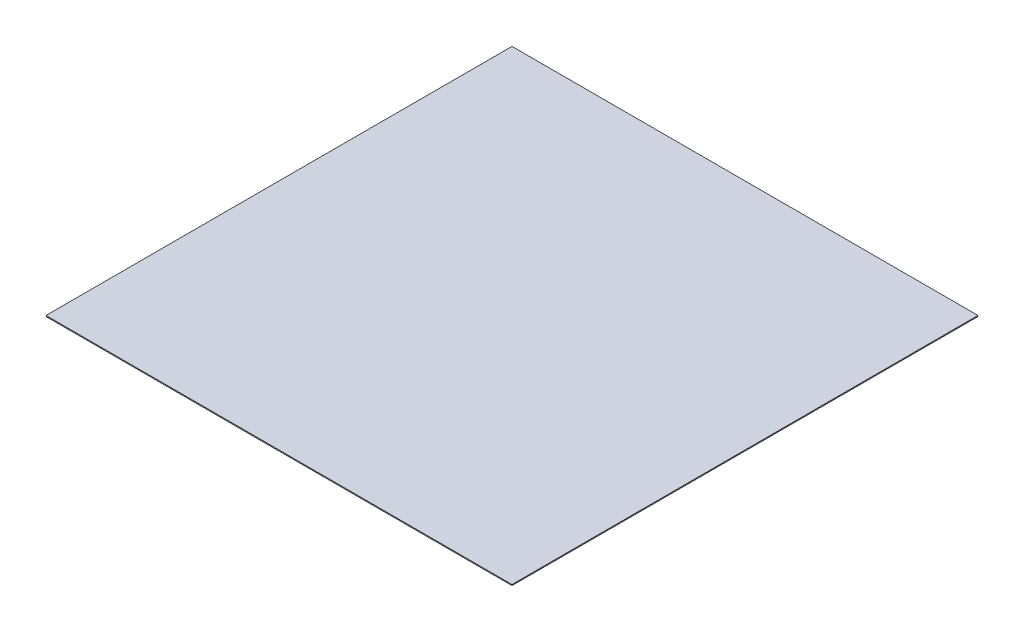
SolidWorks part; units mm, degrees
ref_plane "前视基准面" through (0, 0, 0) normal (0, 0, 1) x (1, 0, 0)
ref_plane "上视基准面" through (0, 0, 0) normal (0, 1, 0) x (1, 0, 0)
ref_plane "右视基准面" through (0, 0, 0) normal (1, 0, 0) x (0, 0, -1)
other "Configuration Table"
sketch "草图1" plane through (0, 0, 0) normal (0, 1, 0) x (1, 0, 0)
  line L1 (-480, 480) -> (480, 480)
  line L2 (-480, 480) -> (-480, -480)
  line L3 (-480, -480) -> (480, -480)
  line L4 (480, 480) -> (480, -480)
  line L5 (-480, 480) -> (480, -480) construction
  line L6 (-480, -480) -> (480, 480) construction
  point P0 (0, 0)
  dimension "D1" = 960
  dimension "D2" = 960
base flange "基体-法兰1" sketch "草图1" thickness 2 reverse thickness direction no parameters "D1"=2.5
sketch "折弯-线1" plane through (0, 0, 0) normal (0, 1, 0) x (1, 0, 0)
sketch "边界框1" plane through (0, 0, 0) normal (0, 1, 0) x (1, 0, 0)
sheet metal parameters "钣金6" thickness 2 parameters "D1"=2.5
flat pattern "平板型式6" [suppressed]
sketch "折弯-线2" plane through (0, 0, 0) normal (0, 1, 0) x (1, 0, 0)
sketch "边界框2" [suppressed] plane through (0, 0, 0) normal (0, 1, 0) x (1, 0, 0)
